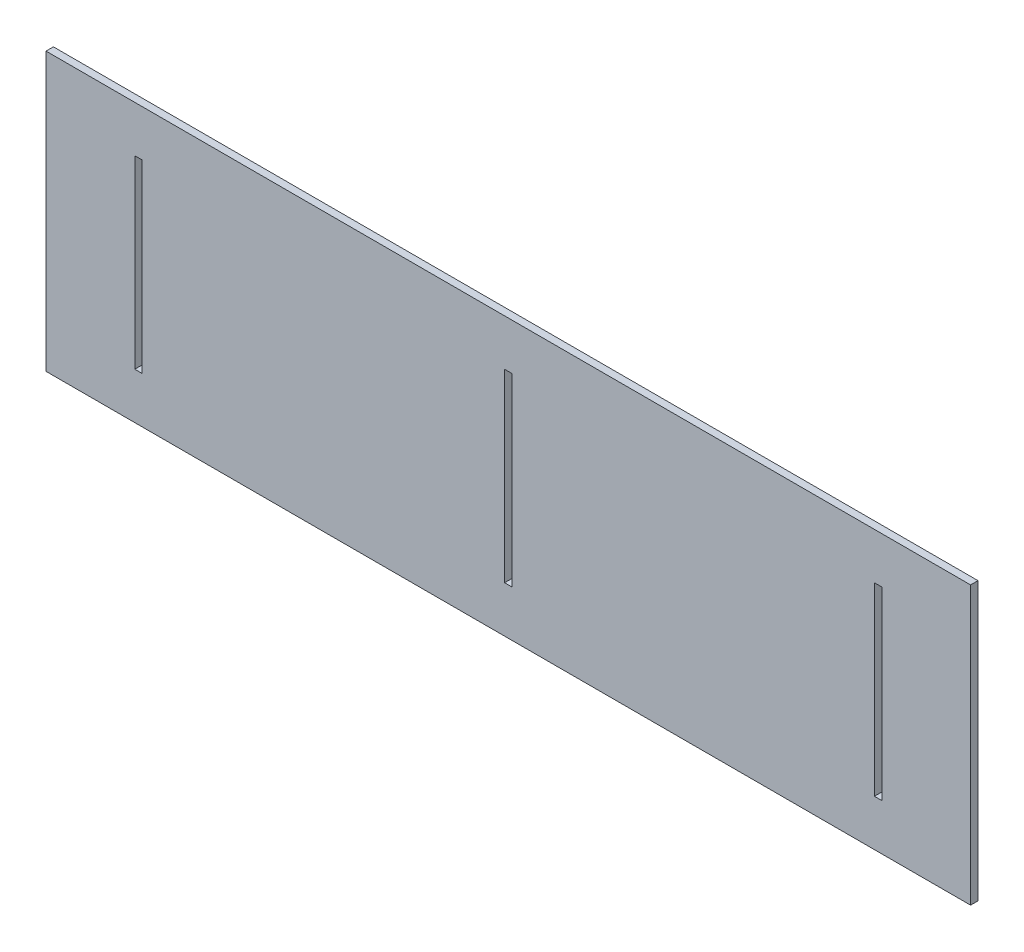
SolidWorks part; units mm, degrees
ref_plane "前视基准面" through (0, 0, 0) normal (0, 0, 1) x (1, 0, 0)
ref_plane "上视基准面" through (0, 0, 0) normal (0, 1, 0) x (1, 0, 0)
ref_plane "右视基准面" through (0, 0, 0) normal (1, 0, 0) x (0, 0, -1)
sketch "草图2" plane through (0, 0, 0) normal (0, 0, 1) x (1, 0, 0)
  line L1 (-73.6818, 78.3847) -> (176.3182, 78.3847)
  line L2 (-73.6818, 78.3847) -> (-73.6818, 3.3847)
  line L3 (-73.6818, 3.3847) -> (176.3182, 3.3847)
  line L4 (176.3182, 78.3847) -> (176.3182, 3.3847)
  point P4 (0, 0)
  point P16 (0, 0)
  dimension "D1" = 250
  dimension "D2" = 75
sketch "草图4" plane through (0, 0, 0) normal (0, 0, 1) x (1, 0, 0)
  line L5 (-73.6818, 78.3847) -> (176.3182, 78.3847) construction
  line L6 (-73.6818, 78.3847) -> (-73.6818, 3.3847) construction
  line L7 (51.3182, 96.8277) -> (51.3182, 60.5853) construction
  line L8 (152.3182, 40.8847) -> (150.3182, 40.8847) construction
  line L9 (151.3182, 15.8847) -> (151.3182, 65.8847) construction
  line L10 (150.3182, 65.8847) -> (150.3182, 15.8847)
  line L11 (-49.6818, 65.8847) -> (-47.6818, 65.8847)
  line L12 (-49.6818, 65.8847) -> (-49.6818, 15.8847)
  line L13 (-49.6818, 15.8847) -> (-47.6818, 15.8847)
  line L14 (-47.6818, 65.8847) -> (-47.6818, 15.8847)
  line L15 (-48.6818, 15.8847) -> (-48.6818, 65.8847) construction
  line L16 (-49.6818, 40.8847) -> (-47.6818, 40.8847) construction
  line L17 (50.3182, 65.8847) -> (52.3182, 65.8847)
  line L18 (50.3182, 65.8847) -> (50.3182, 15.8847)
  line L19 (50.3182, 15.8847) -> (52.3182, 15.8847)
  line L20 (52.3182, 65.8847) -> (52.3182, 15.8847)
  line L21 (51.3182, 15.8847) -> (51.3182, 65.8847) construction
  line L22 (50.3182, 40.8847) -> (52.3182, 40.8847) construction
  line L26 (152.3182, 15.8847) -> (150.3182, 15.8847)
  line L27 (152.3182, 65.8847) -> (152.3182, 15.8847)
  line L28 (152.3182, 65.8847) -> (150.3182, 65.8847)
  point P0 (51.3182, 78.3847)
  point P5 (0, 0)
  point P24 (51.3182, 40.8847)
  point P29 (-48.6818, 40.8847)
  point P34 (51.3182, 40.8847)
  point P35 (151.3182, 40.8847)
  point P36 (0, 0)
  dimension "D1" = 12.5
  dimension "D2" = 50
  dimension "D3" = 2
  dimension "D4" = 50
  dimension "D5" = 2
  dimension "D6" = 24
  dimension "D7" = 12.5
extrude "凸台-拉伸3" add sketch "草图2" along normal blind 2
extrude "切除-拉伸1" cut sketch "草图4" against normal blind 2 and the other way blind 2
